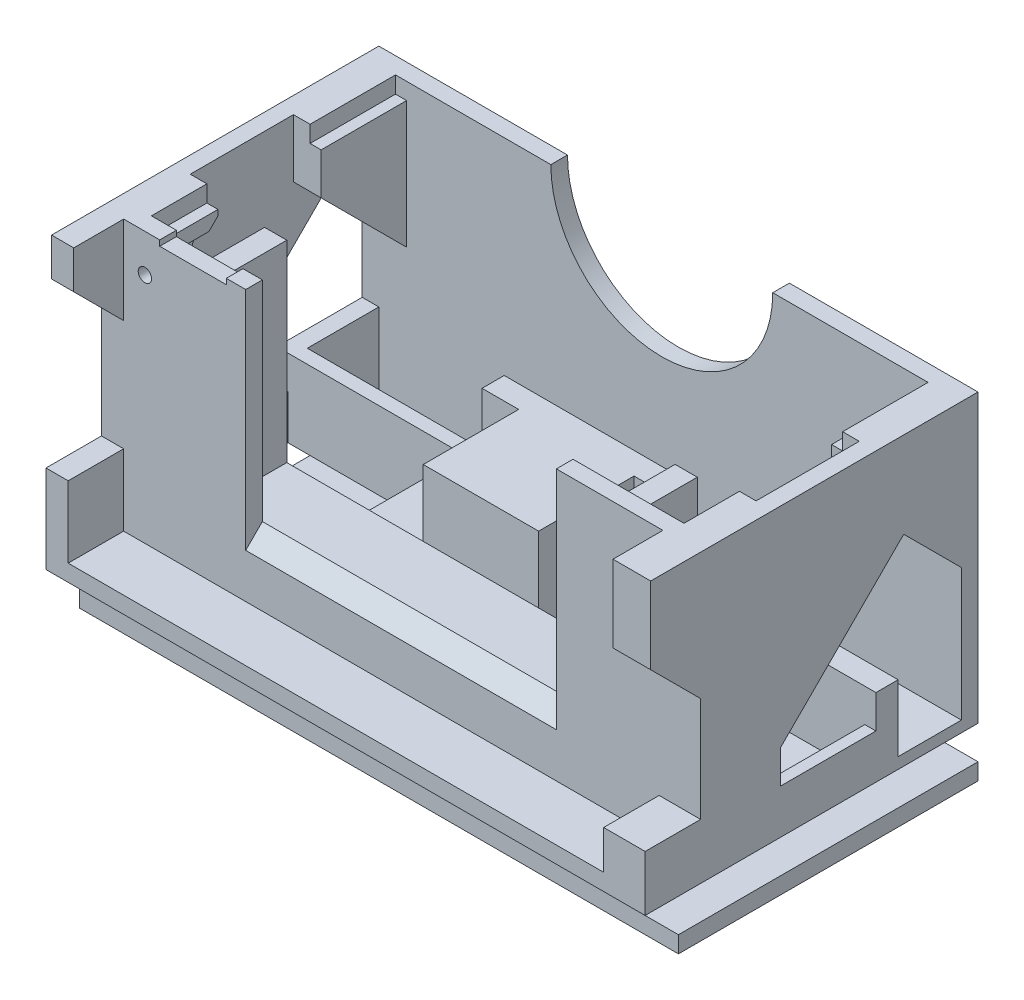
SolidWorks part; units mm, degrees
ref_plane "Front Plane" through (0, 0, 0) normal (0, 0, 1) x (1, 0, 0)
ref_plane "Top Plane" through (0, 0, 0) normal (0, 1, 0) x (1, 0, 0)
ref_plane "Right Plane" through (0, 0, 0) normal (1, 0, 0) x (0, 0, -1)
sketch "Sketch1" plane through (0, 0, 0) normal (0, 1, 0) x (1, 0, 0)
  line L1 (0, 0) -> (54, 0)
  line L2 (0, 0) -> (0, 27)
  line L3 (0, 27) -> (54, 27)
  line L4 (54, 0) -> (54, 27)
  dimension "D1" = 54
  dimension "D2" = 27
extrude "Boss-Extrude1" add sketch "Sketch1" along normal blind 1.5
sketch "Sketch2" plane through (0, 1.5, 0) normal (0, 1, 0) x (1, 0, 0)
  line L0 (0, 27) -> (0, 0) construction
  circle A0 centre (5.8, 13.5) radius 2.25
  point P5 (0, 13.5)
  dimension "D3" = 4.5
  dimension "D1" = 5.8
extrude "Cut-Extrude1" cut sketch "Sketch2" against normal up to next and the other way through all
ref_plane "Plane1" through (27, 0, 0) normal (-1, 0, 0) x (0, 0, 1)
mirror "Mirror1" about plane through (27, 0, 0) normal (-1, 0, 0) of "Cut-Extrude1"
sketch "Sketch3" plane through (0, 1.5, 0) normal (0, 1, 0) x (1, 0, 0)
  line L0 (54, 27) -> (0, 27) construction
  line L1 (13.8, 27) -> (40.2, 27)
  line L2 (13.8, 27) -> (13.8, -3)
  line L3 (13.8, -3) -> (40.2, -3)
  line L4 (40.2, 27) -> (40.2, -3)
  line L7 (0, 0) -> (54, 0) construction
  circle A0 centre (5.8, 13.5) radius 2.25 construction
  point P8 (27, 0)
  point P9 (27, -3)
  dimension "D1" = 8
  dimension "D2" = 3
extrude "Boss-Extrude2" add sketch "Sketch3" along normal blind 3
chamfer "Chamfer3" distance 3 angle 45 1 edges at (27, 1.5, 3)
sketch "Sketch4" plane through (0, 4.5, 0) normal (0, 1, 0) x (1, 0, 0)
  line L0 (54, 0) -> (54, 27) construction
  line L1 (0, 27) -> (54, 27)
  line L2 (0, 27) -> (0, 2)
  line L3 (0, 2) -> (54, 2)
  line L4 (54, 27) -> (54, 2)
  line L5 (0, 27) -> (0, 0) construction
  line L6 (0, 17.8) -> (54, 17.8)
  line L7 (0, 17.8) -> (0, 9.2)
  line L8 (0, 9.2) -> (54, 9.2)
  line L9 (54, 17.8) -> (54, 9.2)
  line L10 (40.2, 27) -> (13.8, 27) construction
  line L11 (0, 27) -> (0, 0) construction
  line L13 (32.2, 17.8) -> (21.8, 17.8)
  line L14 (32.2, 17.8) -> (32.2, 9.2)
  line L15 (32.2, 9.2) -> (21.8, 9.2)
  line L16 (21.8, 17.8) -> (21.8, 9.2)
  line L17 (40.2, 0) -> (54, 0) construction
  point P0 (0, 13.5)
  point P17 (0, 13.5)
  point P23 (27, 17.8)
  point P24 (27, 17.8)
  line M9 (13.8, 27) -> (13.8, -3)
  line M11 (40.2, -3) -> (40.2, 27)
  line M12 (40.2, 27) -> (13.8, 27)
  dimension "D1" = 8.6
  dimension "D2" = 21.8
  dimension "D3" = 2
extrude "Boss-Extrude3" add sketch "Sketch4" along normal blind 7 contours L2 L6 L1 M9 | L6 M9 M11 M12 | L6 L4 L1 M11 | L8 L3 L4 M11 | L8 M9 M11 | L8 L2 L3 M9 | L14 L13 L16 L15 region at (6.9, 4.5, -22.4) region at (27, 4.5, -22.4) region at (47.1, 4.5, -22.4) region at (6.9, 4.5, -5.6) region at (27, 4.5, -5.6) region at (47.1, 4.5, -5.6)
sketch "Sketch25" plane through (54, 0, 0) normal (1, 0, 0) x (0, 0, -1)
  line L0 (17.8, 11.5) -> (17.8, 4.5) construction
  line L1 (9.2, 4.5) -> (17.8, 4.5)
  line L2 (9.2, 4.5) -> (9.2, 8.5)
  line L3 (9.2, 8.5) -> (17.8, 8.5)
  line L4 (17.8, 4.5) -> (17.8, 8.5)
  dimension "D1" = 4
extrude "Boss-Extrude19" add sketch "Sketch25" against normal blind 1
mirror "Mirror6" about plane through (27, 0, 0) normal (-1, 0, 0) of "Boss-Extrude19"
extrude "Boss-Extrude15" add sketch "Sketch4<4>" along normal blind 6 from surface contours L6 L16 L8 L14 region at (27, 4.5, -13.5) starting at face at (27, 11.5, -13.8333)
sketch "Sketch4<4>" plane through (0, 4.5, 0) normal (0, 1, 0) x (1, 0, 0) same geometry as "Sketch4"
sketch "Sketch5" plane through (0, 11.5, 0) normal (0, 1, 0) x (1, 0, 0)
  line L0 (54, 9.2) -> (54, 2) construction
  line L1 (54, 2) -> (0, 2)
  line L2 (54, 2) -> (54, 3.5)
  line L3 (54, 3.5) -> (0, 3.5)
  line L4 (0, 2) -> (0, 3.5)
  line L5 (0, 9.2) -> (0, 2) construction
  line L6 (32.2, 9.2) -> (54, 9.2) construction
  line L7 (27, 0.825) -> (27, -0.825) construction
  line L16 (9.5, 9.2) -> (7.5, 9.2)
  line L17 (44.5, 3.5) -> (46.5, 3.5)
  line L18 (44.5, 3.5) -> (44.5, 9.2)
  line L19 (44.5, 9.2) -> (46.5, 9.2)
  line L20 (46.5, 3.5) -> (46.5, 9.2)
  line L21 (7.5, 3.5) -> (7.5, 9.2)
  line L22 (9.5, 3.5) -> (7.5, 3.5)
  line L23 (9.5, 3.5) -> (9.5, 9.2)
  line L27 (52.225, 2) -> (46.225, 2)
  line L29 (1.775, 2) -> (7.775, 2)
  line L33 (0, 27) -> (0, 17.8) construction
  line L34 (54, 27) -> (0, 27)
  line L35 (54, 27) -> (54, 25.5)
  line L36 (54, 25.5) -> (0, 25.5)
  line L37 (0, 27) -> (0, 25.5)
  line M16 (21.8, 9.2) -> (0, 9.2)
  line M20 (54, 9.2) -> (32.2, 9.2)
  dimension "D1" = 22
  dimension "D2" = 1.5
  dimension "D3" = 19.5
  dimension "D4" = 2
  dimension "D7" = 1.5
extrude "Boss-Extrude5" add sketch "Sketch5" along normal offset from surface (18.86 mm away) 25.86 contours L3 L4 L1 L2 up to face at (27, 4.5, 0.5) offset beyond the face yes
extrude "Boss-Extrude6" add sketch "Sketch5<3>" along normal offset from surface (17.36 mm away) 1.5 contours L3 L20 L18 M20 | L3 L23 L21 M16 region at (45.5, 11.5, -6.35) region at (8.5, 11.5, -6.35) up to face at (27, 30.36, -2.75)
sketch "Sketch5<3>" plane through (0, 11.5, 0) normal (0, 1, 0) x (1, 0, 0) same geometry as "Sketch5"
extrude "Boss-Extrude12" add sketch "Sketch4<3>" along normal offset from surface (3.86 mm away) 20.5 contours L16 L6 L8 M9 | L6 L14 L8 M11 region at (17.8, 4.5, -13.5) region at (36.2, 4.5, -13.5) up to face at (45.5, 28.86, -6.35)
sketch "Sketch4<3>" plane through (0, 4.5, 0) normal (0, 1, 0) x (1, 0, 0) same geometry as "Sketch4"
sketch "Sketch17" plane through (0, 0, -2) normal (0, 0, 1) x (1, 0, 0)
  line L0 (54, 30.36) -> (54, 4.5) construction
  line L1 (0, 4.5) -> (54, 4.5)
  line L2 (0, 4.5) -> (0, 6)
  line L3 (0, 6) -> (54, 6)
  line L4 (54, 4.5) -> (54, 6)
  line L5 (54, 30.36) -> (0, 30.36) construction
  line L10 (0, 30.36) -> (2, 30.36)
  line L11 (0, 30.36) -> (0, 6)
  line L12 (0, 6) -> (2, 6)
  line L13 (2, 30.36) -> (2, 6)
  line L14 (2, 22.43) -> (0, 22.43)
  line L15 (2, 22.43) -> (2, 12.43)
  line L16 (2, 12.43) -> (0, 12.43)
  line L17 (0, 22.43) -> (0, 12.43)
  line L23 (54, 6) -> (50.26, 6)
  line L24 (54, 30.36) -> (50.6, 30.36)
  line L25 (54, 30.36) -> (54, 18.93)
  line L26 (54, 18.93) -> (50.6, 18.93)
  line L27 (50.6, 30.36) -> (50.6, 18.93)
  line L28 (54, 6) -> (54, 9.5)
  line L29 (54, 9.5) -> (50.26, 9.5)
  line L30 (50.26, 6) -> (50.26, 9.5)
  point P18 (2, 17.43)
  point P20 (52.3, 18.93)
  line M21 (0, 4.5) -> (13.8, 4.5)
  line M22 (13.8, 4.5) -> (40.2, 4.5)
  line M23 (40.2, 4.5) -> (54, 4.5)
  line M24 (54, 4.5) -> (54, 30.36)
  line M25 (54, 30.36) -> (0, 30.36)
  line M26 (0, 30.36) -> (0, 4.5)
  dimension "D1" = 1.5
  dimension "D2" = 48.6
  dimension "D3" = 2
  dimension "D4" = 10
  dimension "D5" = 11.43
  dimension "D6" = 11.43
  dimension "D7" = 5
extrude "Boss-Extrude13" add sketch "Sketch17" along normal up to vertex (5 mm away) contours L13 L16 L3 M26 | L3 M26 M21 M22 M23 M24 | L28 L23 L30 L29 region at (27, 5.25, -2) region at (1, 9.215, -2) up to point (13.8, 4.5, 3)
extrude "Boss-Extrude16" add sketch "Sketch17<3>" along normal offset from surface (4.5 mm away) 0.5 contours L14 L13 M25 M26 | L27 L26 M25 M24 region at (1, 26.395, -2) region at (52.3, 24.645, -2) up to face at (26.652, 7.386, 3)
sketch "Sketch17<3>" plane through (0, 0, -2) normal (0, 0, 1) x (1, 0, 0) same geometry as "Sketch17"
chamfer "Chamfer7" distance 4.5 angle 45 2 edges at (52.3, 18.93, 2.5) (1, 22.43, 2.5)
extrude "Boss-Extrude8" add sketch "Sketch5<4>" along normal up to surface (18.86 mm away) contours L36 region at (27, 11.5, -26.25) up to face at (26.65, 30.36, -0.125)
sketch "Sketch5<4>" plane through (0, 11.5, 0) normal (0, 1, 0) x (1, 0, 0) same geometry as "Sketch5"
sketch "Sketch10" plane through (0, 0, 0) normal (-1, 0, 0) x (0, 0, 1)
  line L0 (-3.5, 30.36) -> (-25.5, 30.36)
  line L1 (-3.5, 30.36) -> (-3.5, 11.5) construction
  line L2 (-25.5, 30.36) -> (-25.5, 11.5) construction
  line L3 (-25.5, 30.36) -> (-25.5, 11.5)
  line L6 (-3.5, 11.5) -> (-3.5, 30.36)
  line L8 (-9.2, 11.5) -> (-3.5, 11.5) construction
  line L9 (-3.5, 30.36) -> (-9.2, 30.36)
  line L10 (-3.5, 30.36) -> (-3.5, 11.5)
  line L11 (-3.5, 11.5) -> (-9.2, 11.5)
  line L12 (-9.2, 30.36) -> (-9.2, 11.5)
  line L13 (-9.2, 28.86) -> (-9.2, 11.5) construction
  line L14 (-25.5, 11.5) -> (-17.8, 11.5) construction
  line L15 (-25.5, 30.36) -> (-19.35, 30.36)
  line L16 (-25.5, 30.36) -> (-25.5, 11.5)
  line L17 (-25.5, 11.5) -> (-19.35, 11.5)
  line L19 (2.5, 30.36) -> (-3.5, 30.36) construction
  line L21 (-25.5, 27.8) -> (-9.2, 11.5)
  line M36 (-3.5, 30.36) -> (-3.5, 11.5)
  line M37 (-3.5, 11.5) -> (-9.2, 11.5)
  dimension "D1" = 0
  dimension "D4" = 45
extrude "Boss-Extrude9" add sketch "Sketch10" against normal blind 1.5 contours L0 L12 M37 M36 | L16 L21 L12 L0
mirror "Mirror3" about plane through (27, 0, 0) normal (-1, 0, 0) of "Boss-Extrude9"
sketch "Sketch18" plane through (0, 30.36, 0) normal (0, 1, 0) x (1, 0, 0)
  line L0 (52.5, 25.5) -> (1.5, 25.5) construction
  line L1 (0, 25.5) -> (4, 25.5)
  line L2 (0, 25.5) -> (0, 17.8)
  line L3 (0, 17.8) -> (4, 17.8)
  line L4 (4, 25.5) -> (4, 17.8)
  line L5 (27, 0.825) -> (27, -0.825) construction
  line L6 (52.5, 8.5) -> (50, 8.5)
  line L7 (1.5, 3.5) -> (4, 3.5)
  line L8 (0, 17.8) -> (21.8, 17.8) construction
  line L9 (54, 17.8) -> (50, 17.8)
  line L10 (50, 25.5) -> (50, 17.8)
  line L11 (54, 25.5) -> (50, 25.5)
  line L12 (54, 25.5) -> (54, 17.8)
  line L13 (0, -2.5) -> (0, 27) construction
  line L14 (1.5, 3.5) -> (1.5, 8.5)
  line L15 (1.5, 8.5) -> (4, 8.5)
  line L16 (4, 3.5) -> (4, 8.5)
  line L17 (50, 3.5) -> (50, 8.5)
  line L18 (52.5, 3.5) -> (50, 3.5)
  line L19 (52.5, 3.5) -> (52.5, 8.5)
  line M5 (52.5, 25.5) -> (52.5, 3.5)
  line M6 (52.5, 3.5) -> (1.5, 3.5)
  line M8 (1.5, 25.5) -> (52.5, 25.5)
  line M10 (0, 27) -> (0, -2.5)
  line M16 (54, -2.5) -> (54, 27)
  dimension "D1" = 23
  dimension "D2" = 5
extrude "Boss-Extrude14" add sketch "Sketch18" against normal blind 13 contours L11 L9 M16 M5 | L10 L9 M8 M5 | L4 L3 M8 | L3 L1 M10 | L4 L3 L2 L1 region at (51.25, 30.36, -21.65) region at (2, 30.36, -21.65) region at (53.25, 30.36, -21.65)
extrude "Boss-Extrude17" add sketch "Sketch18<3>" against normal blind 7 contours L16 L15 M6 | L17 L6 M6 M5 region at (51.25, 30.36, -6) region at (2.75, 30.36, -6)
sketch "Sketch18<3>" plane through (0, 30.36, 0) normal (0, 1, 0) x (1, 0, 0) same geometry as "Sketch18"
chamfer "Chamfer8" distance 5 angle 45 2 edges at (51.25, 23.36, -8.5) (2.75, 23.36, -8.5)
chamfer "Chamfer6" distance 7.75 angle 45 2 edges at (2, 17.36, -17.8) (52, 17.36, -17.8)
sketch "Sketch20" plane through (0, 30.36, 0) normal (0, 1, 0) x (1, 0, 0)
  line L0 (0, 17.8) -> (21.8, 17.8) construction
  line L1 (4, 25.5) -> (3, 25.5)
  line L2 (4, 25.5) -> (4, 17.8)
  line L3 (4, 17.8) -> (3, 17.8)
  line L4 (3, 25.5) -> (3, 17.8)
  line L5 (27, 0.825) -> (27, -0.825) construction
  line L6 (50, 17.8) -> (51, 17.8)
  line L7 (51, 25.5) -> (51, 17.8)
  line L8 (50, 25.5) -> (51, 25.5)
  line L9 (50, 25.5) -> (50, 17.8)
  line L10 (50, 3.5) -> (4, 3.5) construction
  line L11 (4, 8.5) -> (3, 8.5)
  line L12 (4, 8.5) -> (4, 3.5)
  line L13 (4, 3.5) -> (3, 3.5)
  line L14 (3, 8.5) -> (3, 3.5)
  line L15 (50, 3.5) -> (51, 3.5)
  line L16 (51, 8.5) -> (51, 3.5)
  line L17 (50, 8.5) -> (51, 8.5)
  line L18 (50, 8.5) -> (50, 3.5)
  dimension "D1" = 1
  dimension "D2" = 1
extrude "Cut-Extrude7" cut sketch "Sketch20" against normal up to surface (1.5 mm away) up to face at (8.5, 28.86, -6.35)
sketch "Sketch22" plane through (0, 30.36, 0) normal (0, 1, 0) x (1, 0, 0)
  line L0 (50.6, 2) -> (2, 2) construction
  line L1 (5.25, 2) -> (11.25, 2)
  line L2 (5.25, 2) -> (5.25, 3.5)
  line L3 (5.25, 3.5) -> (11.25, 3.5)
  line L4 (11.25, 2) -> (11.25, 3.5)
  line L5 (51, 3.5) -> (3, 3.5) construction
  line L6 (3, 8.5) -> (3, 3.5) construction
  dimension "D1" = 6
  dimension "D2" = 2.25
extrude "Cut-Extrude10" cut sketch "Sketch22" against normal offset from surface (0.5 mm away) 1 up to face at (8.5, 28.86, -6.35)
sketch "Sketch12" plane through (0, 0, -2) normal (0, 0, 1) x (1, 0, 0)
  line L1 (13, 30.36) -> (41, 30.36)
  line L3 (13, 30.36) -> (13, 11.5)
  line L4 (13, 11.5) -> (41, 11.5)
  line L5 (41, 30.36) -> (41, 11.5)
  line L6 (52.5, 30.36) -> (1.5, 30.36) construction
  line L7 (44.5, 11.5) -> (9.5, 11.5) construction
  point P11 (27, 30.36)
  point P12 (27, 30.36)
  dimension "D1" = 28
extrude "Cut-Extrude2" cut sketch "Sketch12" against normal up to surface (7.2 mm away) up to face at (45.6385, 12.1492, -9.2)
sketch "Sketch14" plane through (0, 0, -27) normal (0, 0, -1) x (-1, 0, 0)
  line L1 (-54, 30.36) -> (0, 30.36) construction
  line L2 (-37, 30.36) -> (-17, 30.36)
  line L4 (-37, 30.36) -> (-17, 30.36)
  circle A1 centre (-27, 30.36) radius 10
  point P4 (-27, 30.36)
  point P7 (-27, 30.36)
  point P11 (-27, 30.36)
  line M7 (0, 30.36) -> (-54, 30.36)
  dimension "D1" = 20
extrude "Cut-Extrude3" cut sketch "Sketch14" against normal up to next contours A1 M7 | A1 region at (27, 26.1159, -27)
sketch "Sketch15" plane through (0, 11.5, 0) normal (0, 1, 0) x (1, 0, 0)
  line L0 (54, 25.5) -> (54, 17.8) construction
  line L1 (27.5, 17.8) -> (18.5, 17.8)
  line L2 (27.5, 17.8) -> (27.5, 19.8)
  line L3 (27.5, 19.8) -> (18.5, 19.8)
  line L4 (18.5, 17.8) -> (18.5, 19.8)
  line L6 (54, 25.5) -> (0, 25.5) construction
  line L7 (0, 17.8) -> (21.8, 17.8) construction
  dimension "D1" = 35.5
  dimension "D2" = 9
  dimension "D4" = 5.7
extrude "Boss-Extrude11" add sketch "Sketch15" along normal blind 6
mirror "Mirror5" about plane through (27, 0, 0) normal (-1, 0, 0) of "Boss-Extrude11"
sketch "Sketch21" plane through (0, 11.5, 0) normal (0, 1, 0) x (1, 0, 0)
  line L0 (54, 25.5) -> (54, 17.8) construction
  line L1 (0, 25.5) -> (54, 25.5)
  line L2 (0, 25.5) -> (0, 19.8)
  line L3 (0, 19.8) -> (54, 19.8)
  line L4 (54, 25.5) -> (54, 19.8)
  line L5 (18.5, 19.8) -> (35.5, 19.8) construction
  line L6 (18.5, 19.8) -> (18.5, 17.8) construction
  line L7 (0, 25.5) -> (18.5, 25.5)
  line L8 (0, 25.5) -> (0, 19.05)
  line L9 (0, 19.05) -> (18.5, 19.05)
  line L10 (18.5, 25.5) -> (18.5, 19.05)
  line M6 (18.5, 19.8) -> (35.5, 19.8)
  line M9 (54, 17.8) -> (54, 25.5)
  line M10 (54, 25.5) -> (0, 25.5)
  line M11 (0, 25.5) -> (0, 17.8)
  line M13 (18.5, 17.8) -> (18.5, 19.8)
  line M14 (18.5, 19.8) -> (35.5, 19.8)
  dimension "D1" = 0.75
extrude "Cut-Extrude8" cut sketch "Sketch21" against normal blind 6 contours L10 L3 M10 M14 M6 M9 | L10 L1 L3 M11 | L9 L3 M11 M13 region at (9.25, 11.5, -22.65) region at (36.25, 11.5, -22.65) region at (9.25, 11.5, -19.425)
extrude "Cut-Extrude9" cut sketch "Sketch21<3>" against normal up to surface (7 mm away) from surface contours L10 L1 L3 M11 | L9 L3 M11 M13 region at (9.25, 11.5, -22.65) region at (9.25, 11.5, -19.425) up to face at (46.85, 4.5, -12.75) starting at face at (24.1667, 5.5, -21.45)
sketch "Sketch21<3>" plane through (0, 11.5, 0) normal (0, 1, 0) x (1, 0, 0) same geometry as "Sketch21"
fillet "Fillet7" radius 1 2 edges at (1.5, 17.43, -3.5) (52.5, 17.43, -3.5)
sketch "Sketch23" plane through (0, 0, -2) normal (0, 0, 1) x (1, 0, 0)
  line L0 (2, 30.36) -> (2, 22.43) construction
  line L1 (50.6, 30.36) -> (50.6, 18.93) construction
  line L2 (2, 6) -> (50.26, 6) construction
  circle A0 centre (3.91, 26.95) radius 0.6
  circle A1 centre (48.69, 26.95) radius 0.6
  dimension "D1" = 1.2
  dimension "D2" = 1.91
  dimension "D3" = 1.91
  dimension "D4" = 20.95
extrude "Cut-Extrude11" cut sketch "Sketch23" against normal up to next
chamfer "Chamfer9" distance 1.5 angle 45 1 edges at (27, 11.5, -2)
sketch "Sketch24" plane through (0, 0, -19.05) normal (0, 0, -1) x (-1, 0, 0)
  line L0 (-13.8, 4.5) -> (0, 4.5) construction
  line L1 (0, 11.5) -> (-1.5, 11.5)
  line L2 (0, 11.5) -> (0, 4.5)
  line L3 (0, 4.5) -> (-1.5, 4.5)
  line L4 (-1.5, 11.5) -> (-1.5, 4.5)
  line L5 (0, 4.5) -> (0, 11.5) construction
  dimension "D1" = 1.5
extrude "Boss-Extrude18" add sketch "Sketch24" along normal up to next
